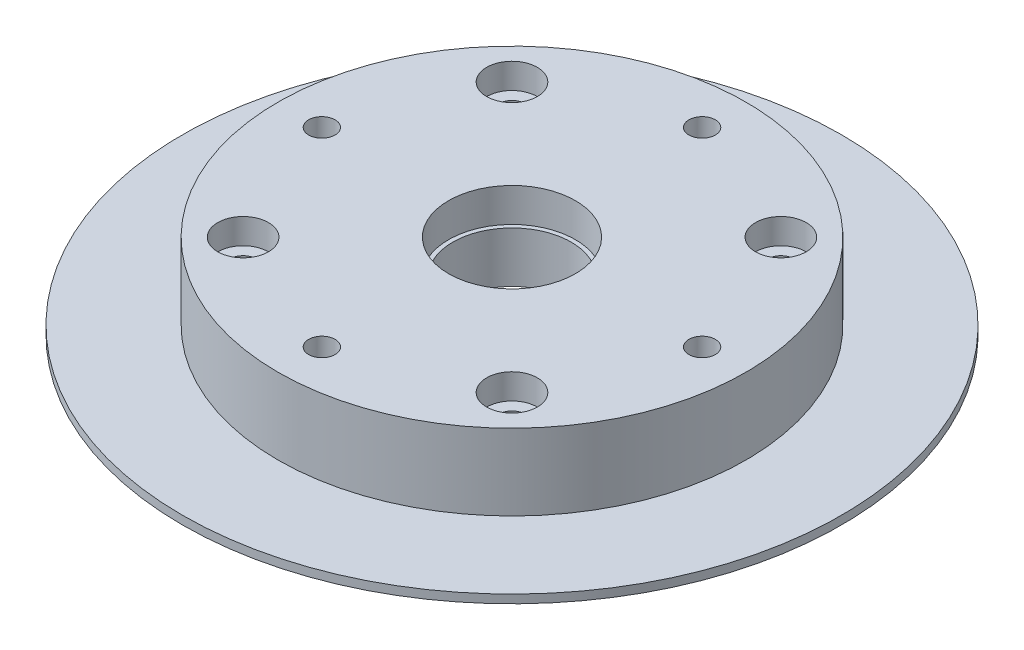
SolidWorks part; units mm, degrees
ref_plane "Front Plane" through (0, 0, 0) normal (0, 0, 1) x (1, 0, 0)
ref_plane "Top Plane" through (0, 0, 0) normal (0, 1, 0) x (1, 0, 0)
ref_plane "Right Plane" through (0, 0, 0) normal (1, 0, 0) x (0, 0, -1)
sketch "Sketch1" plane through (0, 0, 0) normal (0, 1, 0) x (1, 0, 0)
  line L0 (0, 0) -> (22.5, 0) construction
  circle A0 centre (0, 0) radius 39
  circle A1 centre (22.5, 0) radius 1.5635
  circle A2 centre (15.9099, -15.9099) radius 1.5635
  circle A3 centre (0, -22.5) radius 1.5635
  circle A4 centre (-15.9099, -15.9099) radius 1.5635
  circle A5 centre (-22.5, 0) radius 1.5635
  circle A6 centre (-15.9099, 15.9099) radius 1.5635
  circle A7 centre (0, 22.5) radius 1.5635
  circle A8 centre (15.9099, 15.9099) radius 1.5635
  circle A9 centre (0, 0) radius 7.5
  circle A10 centre (0, 0) radius 27.69
  circle A11 centre (0, 0) radius 7
  point P14 (0, 0)
  dimension "D2" = 78
  dimension "D3" = 15
  dimension "D5" = 3.127
  dimension "D6" = 55.38
  dimension "D7" = 14
  dimension "D4" = 22.5
  dimension "D1" = 8
extrude "Boss-Extrude1" add sketch "Sketch1" against normal blind 1 contours A0 A10 | A10 A2 A3 A4 A5 A6 A7 A8 A9 A1 region at (-37.8969, 0, 0) region at (-26.9068, 0, 0)
extrude "Boss-Extrude2" add sketch "Sketch1<3>" along normal blind 9 contours A10 A2 A3 A4 A5 A6 A7 A8 A9 A1 region at (-26.9068, 0, 0)
sketch "Sketch1<3>" plane through (0, 0, 0) normal (0, 1, 0) x (1, 0, 0) same geometry as "Sketch1"
sketch "Sketch2" plane through (0, 9, 0) normal (0, 1, 0) x (1, 0, 0)
  circle A0 centre (15.9099, 15.9099) radius 3
  circle A1 centre (15.9099, -15.9099) radius 3
  circle A2 centre (-15.9099, -15.9099) radius 3
  circle A3 centre (-15.9099, 15.9099) radius 3
  point P12 (0, 0)
  circle M4 centre (-15.9099, -15.9099) radius 1.5635
  circle M6 centre (-15.9099, 15.9099) radius 1.5635
  circle M8 centre (15.9099, 15.9099) radius 1.5635
  dimension "D1" = 6
  dimension "D2" = 4
extrude "Cut-Extrude1" cut sketch "Sketch2" against normal blind 3 contours A3 M6 | A0 M8 | A2 M4 | A1 region at (12.9948, 9, -15.9099) region at (-18.825, 9, 15.9099) region at (-18.825, 9, -15.9099)
extrude "Boss-Extrude3" add sketch "Sketch1<4>" against normal blind 1 contours A11 A9 region at (-7.2879, 0, 0)
sketch "Sketch1<4>" plane through (0, 0, 0) normal (0, 1, 0) x (1, 0, 0) same geometry as "Sketch1"
extrude "Boss-Extrude4" add sketch "Sketch1<5>" along normal blind 5 contours A11 A9 region at (-7.2879, 0, 0)
sketch "Sketch1<5>" plane through (0, 0, 0) normal (0, 1, 0) x (1, 0, 0) same geometry as "Sketch1"
sketch "Sketch3" plane through (0, -1, 0) normal (0, -1, 0) x (1, 0, 0)
  circle A0 centre (22.5, 0) radius 1.925
  circle A1 centre (0, -22.5) radius 1.925
  circle A2 centre (-22.5, 0) radius 1.925
  circle A3 centre (0, 22.5) radius 1.925
  point P12 (0, 0)
  dimension "D1" = 3.85
  dimension "D2" = 4
extrude "Cut-Extrude2" cut sketch "Sketch3" against normal blind 4
equation "\"bearing_21_OD\"= 21mm"
equation "\"pin_cirlce_diameter\"= 75mm"
equation "\"pin_diam\"= 6mm"
equation "\"gear_thickness\"= 4mm"
equation "\"ball_bearing_diam\"= 3.214mm"
equation "\"bearing_21_outer_clearance\"= 0.127mm'change this"
equation "\"bearing_15_OD\"= 15mm"
equation "\"bearing_15_outer_clearance\"= 0mm'change this"
equation "\"thrust_bearing_thickness\"= 5mm'measure this irl and change"
equation "\"D3@Sketch1\"=\"bearing_15_OD\""
equation "\"D1@Boss-Extrude2\"=\"thrust_bearing_thickness\"+4mm"
equation "\"D1@Boss-Extrude4\"=\"thrust_bearing_thickness\""
